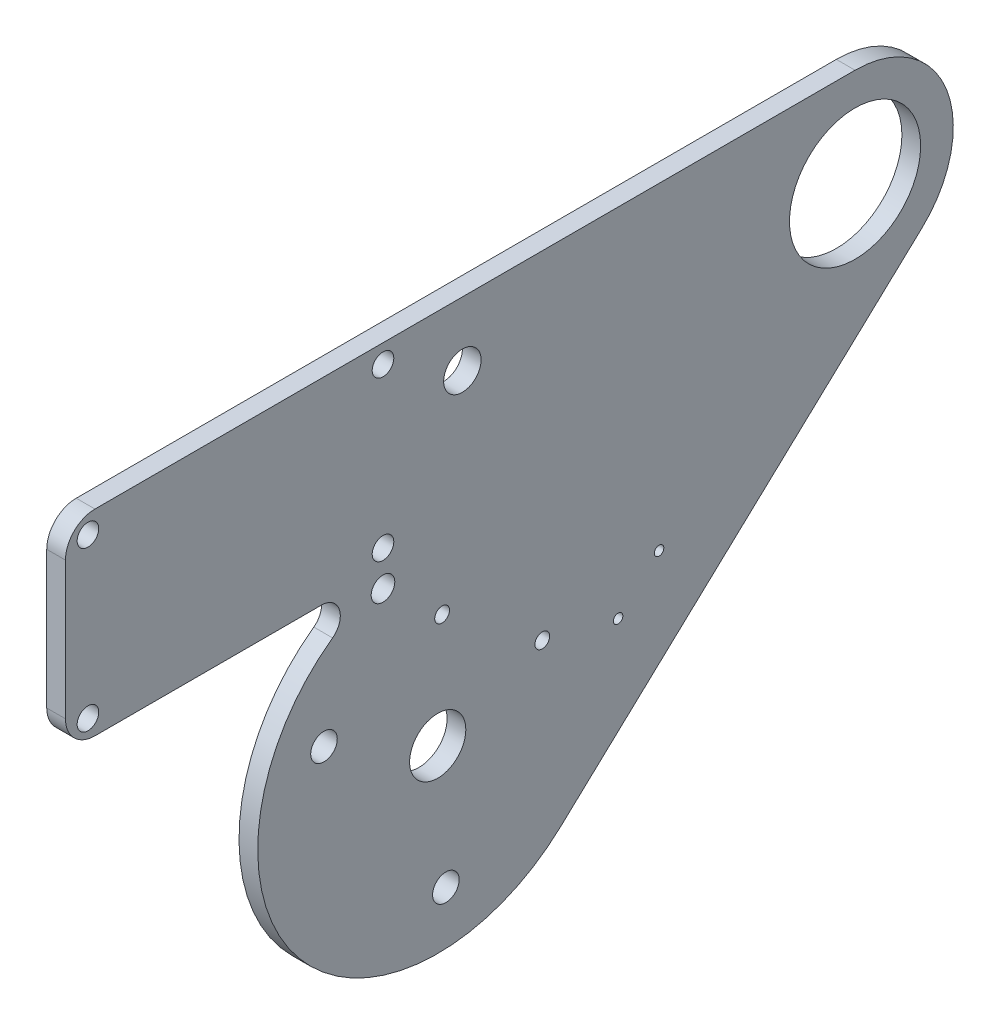
SolidWorks part; units mm, degrees
material "6061 Alloy"
ref_plane "Front Plane" through (0, 0, 0) normal (0, 0, 1) x (1, 0, 0)
ref_plane "Top Plane" through (0, 0, 0) normal (0, 1, 0) x (1, 0, 0)
ref_plane "Right Plane" through (0, 0, 0) normal (1, 0, 0) x (0, 0, -1)
sketch "Sketch1" plane through (0, 0, 0) normal (1, 0, 0) x (0, 0, -1)
  line L0 (-49.9001, -69.4268) -> (11.3662, -12.16)
  line L1 (-133.81, 16.645) -> (-76.19, 16.645)
  line L2 (-133.81, 16.645) -> (-133.81, -16.645)
  line L3 (-133.81, -16.645) -> (-76.19, -16.645)
  line L4 (-76.19, 16.645) -> (-76.19, -16.645)
  line L5 (-130, 13.475) -> (-80, 13.475)
  line L6 (-130, 13.475) -> (-130, -13.475)
  line L7 (-130, -13.475) -> (-80, -13.475)
  line L8 (-80, 13.475) -> (-80, -13.475)
  line L9 (-76.19, 16.645) -> (0, 16.645)
  line L10 (-83.2811, -19.3484) -> (-6.8511, 15.1697)
  line L11 (-130, -13.475) -> (-130, -19.435)
  line L12 (-80, -13.475) -> (-80, -19.435)
  line L13 (-76.19, -16.645) -> (0, -16.645)
  circle A0 centre (0, 0) radius 11.1125
  circle A1 centre (-70.7273, -47.145) radius 4.7625
  circle A2 centre (-70.7273, -47.145) radius 23.015 construction
  circle A3 centre (-70.7273, -47.145) radius 30.5
  circle A4 centre (0, 0) radius 16.645
  circle A5 centre (-130, -19.435) radius 2
  circle A6 centre (-80, -19.435) radius 2
  point P4 (-133.81, 0)
  point P12 (-130, 0)
  dimension "D6" = 22.225
  dimension "D7" = 9.525
  dimension "D8" = 46.03
  dimension "D9" = 61
  dimension "D11" = 0
  dimension "D14" = 4
  dimension "D1" = 33.29
  dimension "D2" = 80
  dimension "D3" = 26.95
  dimension "D4" = 50
  dimension "D5" = 3.81
  dimension "D10" = 85
  dimension "D12" = 3.81
  dimension "D13" = 5.96
extrude "Boss-Extrude1" add sketch "Sketch1" along normal mid plane 3.175 contours A6 A3 A1 | A4 L13 A3 L0 | A4 A0 | A4 L10 L4 L13 | A4 L9 L4 L10 | L8 L12 L3 L10 L4 L1 L2 L11 L6 L5 | L8 L5 L6 L7 | L12 L7 L11 L3 | A6 A3 L13 L3 L10 | L10 L3 L4 | A3 A6 | A3 A6 L10 L12 | L10 A6 A3 L12 | A6 L10 A3 region at (0, -30.4378, 28.398) region at (0, -63.5833, 95.3881) region at (0, -15.0453, -5.9367) region at (0, -18.8843, 82.226) region at (0, -7.4928, 34.7947) region at (0, -18.2558, 80.7031) region at (0, -19.6484, 79.9286) region at (0, -17.0177, 76.5839) region at (0, 5.7227, 51.9516) region at (0, -17.8085, 79.5096) region at (0, -16.4786, 76.5584) region at (0, -15.7889, 77.0165) region at (0, -15.06, 105) region at (0, 0, 105)
hole_wizard "#6 Clearance Hole1" positions "Sketch2" profile "Sketch3" hole size "#6" standard "ANSI Inch" end condition up to next
sketch "Sketch2" plane through (1.5875, 0, 0) normal (1, 0, 0) x (0, 0, -1)
  point P0 (-80, -13.475)
  point P3 (-80, 13.475)
  point P6 (-130, 13.475)
  point P9 (-130, -13.475)
sketch "Sketch3" plane through (1.5875, -13.475, 80) normal (0, 1, 0) x (0, 0, -1)
  line L0 (0, 0) -> (0, 3.175)
  line L1 (0, 3.175) -> (1.8288, 3.175)
  line L2 (1.8288, 3.175) -> (1.8288, 0)
  line L5 (1.8288, 0) -> (0, 0)
  line L11 (0, -6.35) -> (0, 107.95) construction
  dimension "Thru Hole Dia." = 3.6576
  dimension "Thru Hole Depth" = 3.175
hole_wizard "M3x0.5 Tapped Hole1" positions "Sketch4" profile "Sketch5" tap size "M3x0.5" standard "ANSI Metric" end condition up to next
sketch "Sketch4" plane through (1.5875, 0, 0) normal (1, 0, 0) x (0, 0, -1)
  line L7 (-70.7273, -47.145) -> (-41.414, -6.6391) construction
  line L9 (-69.9837, -28.2416) -> (-53.0036, -40.5297) construction
  point P121 (-61.4936, -34.3856)
  point P124 (-69.9837, -28.2416)
  point P127 (-53.0036, -40.5297)
  dimension "D1" = 20.96
  dimension "D2" = 15.75
  dimension "D3" = 135
  dimension "D4" = 50
sketch "Sketch5" plane through (1.5875, -40.5297, 53.0036) normal (0, 1, 0) x (0, 0, -1)
  line L0 (0, 0) -> (0, 3.175)
  line L1 (0, 3.175) -> (1.25, 3.175)
  line L2 (1.25, 3.175) -> (1.25, 0)
  line L5 (1.25, 0) -> (0, 0)
  line L11 (0, -6.35) -> (0, 107.95) construction
  dimension "Thru Tap Drill Dia." = 2.5
  dimension "Thru Tap Drill Depth" = 3.175
hole_wizard "M4 Clearance Hole1" positions "Sketch6" profile "Sketch7" hole size "M4" standard "ANSI Metric" end condition up to next
sketch "Sketch6" plane through (1.5875, 0, 0) normal (1, 0, 0) x (0, 0, -1)
  line L0 (-70.7273, -47.145) -> (-69.3449, -68.6005) construction
  line L1 (-70.7273, -47.145) -> (-89.9995, -37.6144) construction
  line L3 (-70.7273, -47.145) -> (0, 0) construction
  point P2 (-69.3449, -68.6005)
  point P16 (-89.9995, -37.6144)
  dimension "D1" = 21.5
  dimension "D2" = 120
  dimension "D3" = 120
sketch "Sketch7" plane through (1.5875, -37.6144, 89.9995) normal (0, 1, 0) x (0, 0, -1)
  line L0 (0, 0) -> (0, 3.175)
  line L1 (0, 3.175) -> (2.25, 3.175)
  line L2 (2.25, 3.175) -> (2.25, 0)
  line L5 (2.25, 0) -> (0, 0)
  line L11 (0, -6.35) -> (0, 107.95) construction
  dimension "Thru Hole Dia." = 4.5
  dimension "Thru Hole Depth" = 3.175
hole_wizard "M2x0.4 Tapped Hole1" positions "Sketch8" profile "Sketch9" tap size "M2x0.4" standard "ANSI Metric" end condition up to next
sketch "Sketch8" plane through (1.5875, 0, 0) normal (1, 0, 0) x (0, 0, -1)
  line L0 (-49.9001, -69.4268) -> (11.3662, -12.16) construction
  line L2 (0, 0) -> (34142.961, -36527.4995) construction
  point P0 (-33.212, -37.2653)
  point P2 (-40.1523, -43.7524)
  dimension "D1" = 12.1
  dimension "D2" = 9.5
  dimension "D3" = 12.1
  dimension "D4" = 49.71
sketch "Sketch9" plane through (1.5875, -37.2653, 33.212) normal (0, 1, 0) x (0, 0, -1)
  line L0 (0, 0) -> (0, 3.175)
  line L1 (0, 3.175) -> (0.8, 3.175)
  line L2 (0.8, 3.175) -> (0.8, 0)
  line L5 (0.8, 0) -> (0, 0)
  line L11 (0, -6.35) -> (0, 107.95) construction
  dimension "Thru Tap Drill Dia." = 1.6
  dimension "Thru Tap Drill Depth" = 3.175
cosmetic thread "Hole Thread1" parameters "D2"=2
cosmetic thread "Hole Thread2" parameters "D2"=2
fillet "Fillet1" radius 5 2 edges at (0, -16.645, 133.81) (0, 16.645, 133.81)
fillet "Fillet2" radius 3.175 1 edges at (0, -16.645, 77.2953)
extrude "Cut-Extrude1" cut sketch "Sketch1<3>" against normal through all both and the other way through all contours A3 A6 | A3 A6 L10 L12 | L12 A6 L10 | L10 A6 A3 L12 | L10 A6 L12 region at (0, -17.9759, 80.8435) region at (0, -18.2558, 80.7031) region at (0, -19.6484, 79.9286) region at (0, -17.6074, 79.7609) region at (0, -17.8085, 79.5096)
sketch "Sketch1<3>" plane through (0, 0, 0) normal (1, 0, 0) x (0, 0, -1) same geometry as "Sketch1"
hole_wizard "1/4 (0.2500) Dowel Hole1" positions "Sketch10" profile "Sketch11" hole size "1/4" standard "ANSI Inch" end condition up to next
sketch "Sketch10" plane through (1.5875, 0, 0) normal (1, 0, 0) x (0, 0, -1)
  line L0 (-66.5458, 5.822) -> (0, 0) construction
  line L2 (-1000, 0) -> (49000, 0) construction
  point P0 (-66.5458, 5.822)
  dimension "D1" = 66.8
  dimension "D2" = 5
sketch "Sketch11" plane through (1.5875, 5.822, 66.5458) normal (0, 1, 0) x (0, 0, -1)
  line L0 (0, 0) -> (0, 3.175)
  line L1 (0, 3.175) -> (3.175, 3.175)
  line L2 (3.175, 3.175) -> (3.175, 0)
  line L5 (3.175, 0) -> (0, 0)
  line L11 (0, -6.35) -> (0, 107.95) construction
  dimension "Thru Hole Dia." = 6.35
  dimension "Thru Hole Depth" = 3.175
